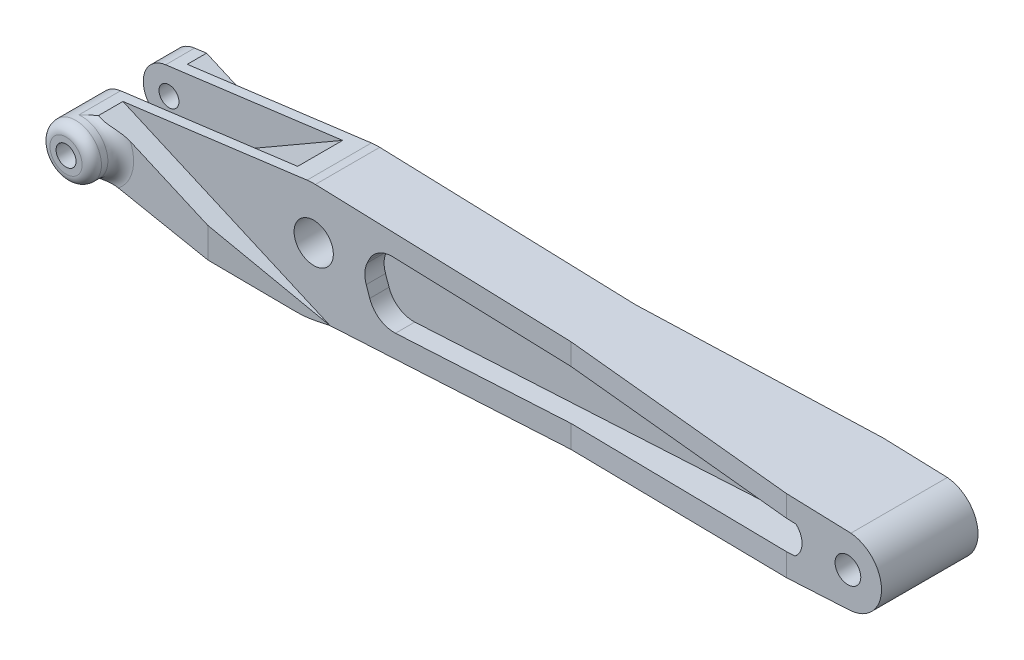
SolidWorks part; units mm, degrees
material "ABS"
ref_plane "Front Plane" through (0, 0, 0) normal (0, 0, 1) x (1, 0, 0)
ref_plane "Top Plane" through (0, 0, 0) normal (0, 1, 0) x (1, 0, 0)
ref_plane "Right Plane" through (0, 0, 0) normal (1, 0, 0) x (0, 0, -1)
sketch "layout" plane through (0, 0, 0) normal (0, 0, 1) x (1, 0, 0)
  line L0 (-107.873, 0) -> (194.2258, 0) construction
  line L1 (0, 80.6323) -> (0, -88.5321) construction
  line L2 (-31.5161, 3.9666) -> (-1.0323, 7.9331)
  line L3 (0.2637, 7.9957) -> (91.1648, 4.9973)
  line L4 (91.2747, -4.9924) -> (0.5495, -9.9849)
  line L5 (-1.9355, -9.8109) -> (-31.7742, -3.9244)
  circle A0 centre (0, 0) radius 3
  circle A1 centre (-31, 0) radius 1.5
  circle A2 centre (91, 0) radius 3
  arc A3 (-31.5161, 3.9666) -> (-31.7742, -3.9244) centre (-31, 0) ccw
  arc A4 (-1.9355, -9.8109) -> (0.5495, -9.9849) centre (0, 0) ccw
  arc A5 (91.2747, -4.9924) -> (91.1648, 4.9973) centre (91, 0) ccw
  arc A7 (-1.0323, 7.9331) -> (0.2637, 7.9957) centre (0, 0) cw
  dimension "D1" = 10
  dimension "D2" = 6
  dimension "D3" = 5
  dimension "D4" = 91
  dimension "D5" = 31
  dimension "D6" = 3
  dimension "D7" = 6
  dimension "D8" = 4
  dimension "D9" = 8
sketch "Sketch2" plane through (0, 0, 0) normal (0, 0, 1) x (1, 0, 0)
  line L0 (0.2637, 7.9957) -> (91.1648, 4.9973) construction
  line L1 (91.2747, -4.9924) -> (0.5495, -9.9849) construction
  line L2 (-1.9355, -9.8109) -> (-31.7742, -3.9244) construction
  line L3 (-31.5161, 3.9666) -> (-1.0323, 7.9331) construction
  line L4 (0.2637, 7.9957) -> (85.9943, 5.1678)
  line L5 (85.9936, -5.2831) -> (0.5495, -9.9849)
  line L6 (-1.9355, -9.8109) -> (-31.7742, -3.9244)
  line L7 (-31.5161, 3.9666) -> (-1.0323, 7.9331)
  arc A1 (-1.9355, -9.8109) -> (0.5495, -9.9849) centre (0, 0) ccw construction
  arc A2 (-31.5161, 3.9666) -> (-31.7742, -3.9244) centre (-31, 0) ccw construction
  arc A4 (85.9936, -5.2831) -> (85.9943, 5.1678) centre (85.5099, -0.0576) ccw
  arc A5 (-1.9355, -9.8109) -> (0.5495, -9.9849) centre (0, 0) ccw
  arc A6 (-31.5161, 3.9666) -> (-31.7742, -3.9244) centre (-31, 0) ccw
  arc A7 (0.2637, 7.9957) -> (-1.0323, 7.9331) centre (0, 0) ccw
  point P4 (0, 0)
  point P5 (0, 0)
  point P9 (0, 0)
  point P10 (0, 0)
  point P14 (0, 0)
  point P15 (0, 0)
  point P18 (0, 0)
  point P19 (0, 0)
  point P20 (0, 0)
  point P21 (0, 0)
  point P22 (0, 0)
  point P24 (0, 0)
  point P26 (0, 0)
  point P27 (0, 0)
  point P28 (0, 0)
  point P29 (0, 0)
  point P30 (0, 0)
  point P31 (0, 0)
  point P32 (0, 0)
  point P33 (0, 0)
  point P34 (0, 0)
  point P35 (0, 0)
  point P36 (0, 0)
  point P37 (0, 0)
  point P38 (0, 0)
  point P39 (0, 0)
  point P40 (0, 0)
  point P41 (0, 0)
extrude "Boss-Extrude1" add sketch "Sketch2" along normal mid plane 15
sketch "Sketch3" plane through (0, 0, 0) normal (0, 0, 1) x (1, 0, 0)
  circle A0 centre (0, 0) radius 2
  dimension "D1" = 4
extrude "Cut-Extrude1" cut sketch "Sketch3" against normal through all both and the other way through all
sketch "Sketch5" plane through (0, 0, 0) normal (0, 0, 1) x (1, 0, 0)
  circle A0 centre (85.5392, 0) radius 2
  point P3 (0, 0)
  point P4 (85.5392, 0)
  dimension "D1" = 4
extrude "Cut-Extrude3" cut sketch "Sketch5" against normal through all both and the other way through all
sketch "Sketch8" plane through (0, 0, 0) normal (0, 0, 1) x (1, 0, 0)
  line L2 (-25.8822, -5.0867) -> (-4, 7.547)
  line L3 (-1.9355, -9.8109) -> (-31.7742, -3.9244) construction
  line L4 (91.1648, 4.9973) -> (0.2637, 7.9957)
  line L5 (0.5495, -9.9849) -> (91.2747, -4.9924)
  line L6 (-31.7742, -3.9244) -> (-1.9355, -9.8109)
  line L7 (-1.0323, 7.9331) -> (-31.5161, 3.9666)
  line L10 (-31.7742, -3.9244) -> (-4, -9.4036)
  line L11 (-4, 7.547) -> (-31.5161, 3.9666)
  line L12 (-4, 7.547) -> (-4, -9.4036) construction
  arc A7 (0.2637, 7.9957) -> (-1.0323, 7.9331) centre (0, 0) ccw
  arc A10 (91.2747, -4.9924) -> (91.1648, 4.9973) centre (91, 0) ccw
  arc A11 (-1.9355, -9.8109) -> (0.5495, -9.9849) centre (0, 0) ccw
  arc A12 (-31.5161, 3.9666) -> (-31.7742, -3.9244) centre (-31, 0) ccw
  arc A16 (-31.5161, 3.9666) -> (-31.7742, -3.9244) centre (-31, 0) ccw
  dimension "D1" = 60
  dimension "D2" = 4
  dimension "D4" = 0
extrude "Cut-Extrude4" cut sketch "Sketch8" against normal mid plane 7 contours L11 A16 L10 L2 region at (-23.0959, 1.4067, 0)
sketch "Sketch9" plane through (0, 0, 0) normal (0, 1, 0) x (1, 0, 0)
  line L0 (105.9892, 0) -> (-59.2384, 0) construction
  line L1 (76, 7.5) -> (40, 5)
  line L2 (85.9943, 7.5) -> (0.2637, 7.5) construction
  line L3 (40, 5) -> (-35, 5)
  line L4 (-35, 7.5) -> (-35, 3.5) construction
  line L5 (-35, 5) -> (-35, 7.5)
  line L6 (-35, 7.5) -> (76, 7.5)
  line L7 (0, 26.3779) -> (0, -48.7291) construction
  line L8 (-35, -7.5) -> (-35, -5)
  line L9 (-35, -3.5) -> (-35, -7.5) construction
  line L10 (-35, -5) -> (40, -5)
  line L11 (40, -5) -> (76, -7.5)
  line L12 (85.9943, -7.5) -> (0.2637, -7.5) construction
  line L13 (76, -7.5) -> (-35, -7.5)
  line L14 (76, 7.5) -> (76, -7.5) construction
  line L15 (40, 5) -> (40, -5) construction
  dimension "D1" = 5
  dimension "D2" = 76
  dimension "D3" = 40
  dimension "D4" = 5
extrude "Cut-Extrude5" cut sketch "Sketch9" against normal through all both and the other way through all
sketch "Sketch4" plane through (0, 0, 0) normal (0, 0, 1) x (1, 0, 0)
  circle A0 centre (0, 0) radius 3.05
  dimension "D1" = 6.1
extrude "Cut-Extrude2" cut sketch "Sketch4" against normal blind 2.6 from surface starting at face at (-2, 0, 5)
sketch "Sketch6" plane through (0, 0, 5) normal (0, 0, 1) x (1, 0, 0)
  line L0 (-29.6594, 4.2082) -> (2.5394, -9.8754)
  line L1 (40, -7.814) -> (0.5495, -9.9849) construction
  line L2 (-31.5161, 3.9666) -> (-1.0323, 7.9331) construction
  line L3 (-1.9355, -9.8109) -> (-31.7742, -3.9244) construction
  line L4 (-31.5161, 3.9666) -> (-29.6594, 4.2082)
  line L5 (2.5394, -9.8754) -> (0.5495, -9.9849)
  line L6 (-1.9355, -9.8109) -> (-31.7742, -3.9244)
  circle A0 centre (-31, 0) radius 5 construction
  arc A1 (-31.5161, 3.9666) -> (-31.7742, -3.9244) centre (-31, 0) ccw construction
  arc A2 (-1.9355, -9.8109) -> (0.5495, -9.9849) centre (0, 0) ccw construction
  arc A3 (-31.5161, 3.9666) -> (-31.7742, -3.9244) centre (-31, 0) ccw
  arc A4 (-1.9355, -9.8109) -> (0.5495, -9.9849) centre (0, 0) ccw
  circle A5 centre (0, 0) radius 7.5 construction
  dimension "D2" = 10
  dimension "D1" = 15
extrude "Boss-Extrude2" add sketch "Sketch6" along normal blind 3
sketch "Sketch14" plane through (0, 0, 0) normal (0, 1, 0) x (1, 0, 0)
  line L0 (2.5394, -5) -> (2.5394, -8)
  line L1 (2.5394, -8) -> (-13.4606, -8)
  line L2 (2.5394, -8) -> (-29.6594, -8) construction
  line L3 (-13.4606, -8) -> (2.5394, -5)
  dimension "D1" = 16
extrude "Cut-Extrude9" cut sketch "Sketch14" against normal through all both and the other way through all
sketch "Sketch10" plane through (0, 0, 5) normal (0, 0, 1) x (1, 0, 0)
  line L0 (-51.3422, 0) -> (118.5827, 0) construction
  line L1 (7.627, 0) -> (9.6935, 4.3624)
  line L2 (9.6935, 4.3624) -> (77.4646, 2.127)
  line L3 (77.3124, -2.2555) -> (9.6935, -5.9764)
  line L4 (9.6935, -5.9764) -> (7.627, 0)
  line L6 (40, 6.685) -> (76, 5.4975) construction
  line L7 (0.2637, 7.9957) -> (40, 6.685) construction
  line L8 (40, -7.814) -> (2.5394, -9.8754) construction
  arc A1 (77.3124, -2.2555) -> (77.4646, 2.127) centre (75.5392, 0) ccw
  circle A2 centre (85.5392, 0) radius 2 construction
  point P12 (0, 0)
  point P13 (0, 0)
  point P19 (73.8554, -5.6999)
  point P20 (72.5392, 0)
  point P21 (72.7553, -2.5062)
  point P22 (73.6941, 2.2513)
  point P23 (0, 0)
  point P24 (0, 0)
  point P25 (72.5392, 0)
  point P26 (75.2298, -2.3701)
  point P27 (76.5701, 2.1565)
  point P28 (77.4646, -2.2555)
  dimension "D3" = 10
  dimension "D1" = 3.3204
  dimension "D2" = 3.5
extrude "Cut-Extrude6" cut sketch "Sketch10" against normal offset from surface 2 and the other way through all up to plane "Front Plane"
fillet "Fillet3" radius 4 3 edges at (9.6935, -5.9764, 3.5) (9.6935, 4.3624, 3.5) (7.627, 0, 3.5)
mirror "Mirror1" about plane through (0, 0, 0) normal (0, 0, 1) of "Cut-Extrude9", "Fillet3", "Cut-Extrude6", "Boss-Extrude2"
sketch "Sketch11" plane through (0, 0, 0) normal (0, 0, 1) x (1, 0, 0)
  circle A0 centre (-31, 0) radius 1.55
  dimension "D1" = 3.1
extrude "Cut-Extrude7" cut sketch "Sketch11" against normal through all both and the other way through all
extrude "Cut-Extrude8" cut sketch "Sketch4<2>" along normal through all from surface starting at face at (2, 0, -5)
sketch "Sketch4<2>" plane through (0, 0, 0) normal (0, 0, 1) x (1, 0, 0) same geometry as "Sketch4"
sketch "Sketch13" plane through (0, 0, 8) normal (0, 0, 1) x (1, 0, 0)
  circle A1 centre (-31, 0) radius 4
  circle A4 centre (-31, 0) radius 1.55 construction
  circle A5 centre (-31, 0) radius 1.55
extrude "Boss-Extrude3" add sketch "Sketch13" along normal blind 4.5
fillet "Fillet7" radius 2 1 edges at (-27.0021, -0.1307, 8)
fillet "Fillet8" radius 1.5 1 edges at (-27, 0, 12.5)
